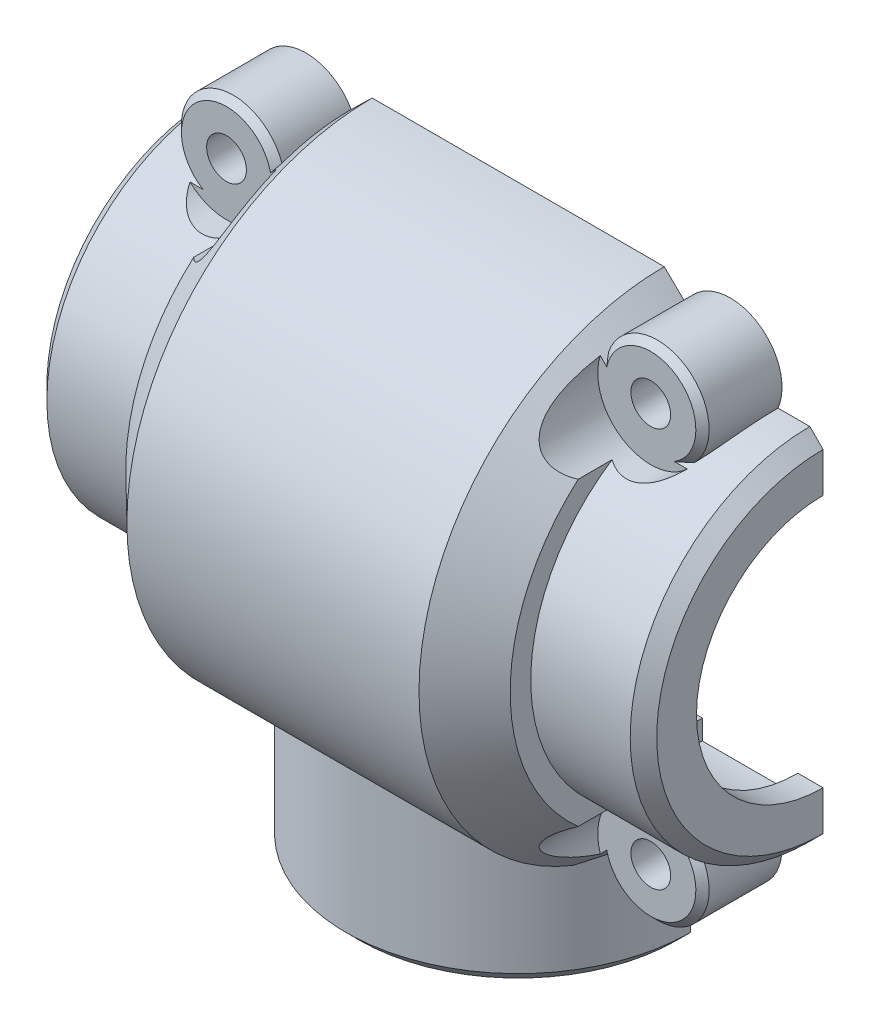
SolidWorks part; units mm, degrees
ref_plane "Front Plane" through (0, 0, 0) normal (0, 0, 1) x (1, 0, 0)
ref_plane "Top Plane" through (0, 0, 0) normal (0, 1, 0) x (1, 0, 0)
ref_plane "Right Plane" through (0, 0, 0) normal (1, 0, 0) x (0, 0, -1)
sketch "Sketch1" plane through (0, 0, 0) normal (0, 0, 1) x (1, 0, 0)
  line L0 (-12, 11.05) -> (-12, -11.05) construction
  line L1 (12, 11) -> (12, -11) construction
  line L2 (-12, 11.05) -> (-23, 11.05) construction
  line L3 (-23, 11.05) -> (-23, -11.05) construction
  line L4 (-23, -11.05) -> (-12, -11.05) construction
  line L5 (-21.1, 11.05) -> (-13.9, 11.05)
  line L6 (-12, 11.05) -> (-12, 14.05)
  line L7 (-12, 14.05) -> (-10, 16)
  line L8 (-10, 16) -> (0, 16)
  line L9 (-23, 13.55) -> (-14.5, 13.55)
  line L10 (-14.5, 13.55) -> (-14.5, 15.1041)
  line L11 (-14.5, 15.1041) -> (-11.017, 18.5)
  line L12 (-11.017, 18.5) -> (0, 18.5)
  line L13 (-23, 13.55) -> (-23, 11.05)
  line L14 (0, 18.5) -> (0, 0) construction
  line L15 (23, 13.55) -> (23, 11.05)
  line L16 (23, 13.55) -> (14.5, 13.55)
  line L17 (21.1, 11.05) -> (13.9, 11.05)
  line L18 (12, 11) -> (12, 14.05)
  line L19 (14.5, 13.55) -> (14.5, 15.1041)
  line L20 (14.5, 15.1041) -> (11.017, 18.5)
  line L21 (12, 14.05) -> (10, 16)
  line L22 (10, 16) -> (0, 16)
  line L23 (11.017, 18.5) -> (0, 18.5)
  line L24 (-23, 0) -> (12, 0) construction
  line L25 (-13.9, 11.05) -> (-12, 11.05) construction
  line L26 (-23, 11.05) -> (-21.1, 11.05) construction
  line L27 (-23, 11.05) -> (-23, 9.55)
  line L28 (-23, 9.55) -> (-21.1, 9.55)
  line L29 (-21.1, 11.05) -> (-21.1, 9.55)
  line L30 (-23, 11.05) -> (-21.1, 9.55) construction
  line L31 (-23, 9.55) -> (-21.1, 11.05) construction
  line L32 (-12, 11.05) -> (-13.9, 11.05) construction
  line L33 (-12, 11.05) -> (-12, 9.55)
  line L34 (-12, 9.55) -> (-13.9, 9.55)
  line L35 (-13.9, 11.05) -> (-13.9, 9.55)
  line L36 (-12, 11.05) -> (-13.9, 9.55) construction
  line L37 (-12, 9.55) -> (-13.9, 11.05) construction
  line L38 (-23, 11.05) -> (-21.1, 11.05) construction
  line L39 (-23, 11.05) -> (-12, 11.05) construction
  line L40 (23, 11.05) -> (23, 9.55)
  line L41 (23, 9.55) -> (21.1, 9.55)
  line L42 (21.1, 11.05) -> (21.1, 9.55)
  line L43 (12, 11) -> (12, 9.55)
  line L44 (12, 9.55) -> (13.9, 9.55)
  line L45 (13.9, 11.05) -> (13.9, 9.55)
  line L46 (13.9, 11.05) -> (12, 11) construction
  line L47 (23, 11.05) -> (21.1, 11.05) construction
  point P4 (-12, 0)
  point P5 (12, 0)
  point P30 (-22.05, 10.3)
  point P34 (-12.95, 10.3)
  point P35 (-12, 10.3)
  point P39 (12, 10.3)
  dimension "D1" = 22.1
  dimension "D2" = 22
  dimension "D3" = 12
  dimension "D4" = 12
  dimension "D5" = 11
  dimension "D6" = 3
  dimension "D7" = 10
  dimension "D8" = 16
  dimension "D10" = 1.5
  dimension "D11" = 1.9
  dimension "D12" = 1.9
  dimension "D13" = 1.5
  dimension "D9" = 2.5
revolve "Revolve1" add sketch "Sketch1" angle 180 about L24 region at (-21.5686, 10.3, 0)
sketch "Sketch2" plane through (0, 0, 0) normal (0, 1, 0) x (1, 0, 0)
  circle A0 centre (0, 0) radius 11
  circle A1 centre (0, 0) radius 4 construction
  dimension "D1" = 22
  dimension "D2" = 8
extrude "Cut-Extrude1" cut sketch "Sketch2" against normal through all
sketch "Sketch3" plane through (0, 0, 0) normal (0, 1, 0) x (1, 0, 0)
  line L0 (13, 0) -> (11, 0)
  line L1 (-11, 0) -> (-13, 0)
  line L2 (11, 0) -> (-11, 0) construction
  arc A0 (-11, 0) -> (11, 0) centre (0, 0) ccw
  arc A1 (-13, 0) -> (13, 0) centre (0, 0) ccw
  arc A2 (13, 0) -> (-13, 0) centre (0, 0) ccw construction
  arc A3 (11, 0) -> (-11, 0) centre (0, 0) ccw construction
  dimension "D1" = 11
  dimension "D2" = 13
extrude "Boss-Extrude1" add sketch "Sketch3" along normal up to surface (9 mm away) from offset 25 contours L0 A0 L1 A1 up to face at (-0.327, 2.2347, 10.6463) offset against normal yes
sketch "Sketch4" plane through (0, 0, 0) normal (0, 0, -1) x (-1, 0, 0)
  line L0 (23, -13.55) -> (14.5, -13.55) construction
  line L1 (14.5, -13.55) -> (14.5, -15.1041) construction
  line L2 (0, 0) -> (23, 0) construction
  line L3 (23, -9.55) -> (23, 9.55) construction
  line L4 (14.5, 13.55) -> (19.6, 13.55)
  line L5 (14.5, 15.1041) -> (14.5, 13.55)
  line L6 (13, 16.5666) -> (14.5, 15.1041)
  line L7 (13, 17.542) -> (13, 16.5666)
  line L8 (0, 18.5) -> (0, -25) construction
  line L9 (-11.017, 18.5) -> (11.017, 18.5) construction
  line L10 (-11, -25) -> (11, -25) construction
  line L11 (-14.5, -13.55) -> (-19.6, -13.55)
  line L12 (-14.5, -15.1041) -> (-14.5, -13.55)
  line L13 (-13, -16.5666) -> (-14.5, -15.1041)
  line L14 (-13, -17.542) -> (-13, -16.5666)
  line L15 (-13, 17.542) -> (-13, 16.5666)
  line L16 (13, -25) -> (13, -16.5666)
  line L17 (13, -16.5666) -> (14.5, -15.1041)
  line L18 (14.5, -15.1041) -> (14.5, -13.55)
  line L19 (14.5, -13.55) -> (23, -13.55)
  line L20 (23, -13.55) -> (23, -9.55)
  line L21 (23, -9.55) -> (21.1, -9.55)
  line L22 (21.1, -9.55) -> (21.1, -11.05)
  line L23 (21.1, -11.05) -> (13.9, -11.05)
  line L24 (13.9, -11.05) -> (13.9, -9.55)
  line L25 (13.9, -9.55) -> (12, -9.55)
  line L26 (12, -9.55) -> (12, -14.05)
  line L27 (12, -14.05) -> (11, -15.025)
  line L28 (11, -15.025) -> (11, -25)
  line L29 (11, -25) -> (13, -25)
  line L30 (13, -17.542) -> (13, -16.5666)
  line L31 (13, -16.5666) -> (14.5, -15.1041)
  line L32 (14.5, -15.1041) -> (14.5, -13.55)
  line L33 (14.5, -13.55) -> (19.6, -13.55)
  line L34 (-13, 16.5666) -> (-14.5, 15.1041)
  line L35 (-14.5, 15.1041) -> (-14.5, 13.55)
  line L36 (-14.5, 13.55) -> (-19.6, 13.55)
  arc A0 (13, -17.542) -> (19.6, -13.55) centre (16, -15.05) ccw
  circle A1 centre (16, -15.05) radius 1.5
  circle A2 centre (16, 15.05) radius 1.5
  arc A3 (13, 17.542) -> (19.6, 13.55) centre (16, 15.05) cw
  arc A4 (-13, 17.542) -> (-19.6, 13.55) centre (-16, 15.05) ccw
  circle A5 centre (-16, 15.05) radius 1.5
  circle A6 centre (-16, -15.05) radius 1.5
  arc A7 (-13, -17.542) -> (-19.6, -13.55) centre (-16, -15.05) cw
  circle A8 centre (16, -15.05) radius 3.9
  circle A9 centre (16, 15.05) radius 3.9
  circle A10 centre (-16, 15.05) radius 3.9
  circle A11 centre (-16, -15.05) radius 3.9
  line M24 (13, -25) -> (13, -16.5666)
  line M25 (13, -16.5666) -> (14.5, -15.1041)
  line M26 (14.5, -15.1041) -> (14.5, -13.55)
  line M27 (14.5, -13.55) -> (23, -13.55)
  dimension "D1" = 3
  dimension "D2" = 7.8
  dimension "D3" = 0
extrude "Boss-Extrude2" add sketch "Sketch4" against normal blind 6 contours L7 A9 L4 L5 L6 | A3 L7 L6 L5 A2 L4 | L4 A2 L5 | A1 A0 L33 M26 M25 M24 | L33 A8 L32 M24 M25 M26 M27 | A1 L32 M27 | A5 L35 L34 L15 A4 L36 | L36 A10 L15 L34 L35 | A5 L36 L35 | L11 A6 L12 | L14 A11 L11 L12 L13 | A7 L14 L13 L12 A6 L11 region at (-14.8351, 13.8851, 0) region at (-15.0756, 13.3566, 0) region at (-16.8249, 16.5395, 0) region at (14.8351, -13.8851, 0) region at (15.0756, -13.3566, 0) region at (16.8249, -16.5395, 0) region at (15.0756, 13.3566, 0) region at (16.8249, 16.5395, 0) region at (14.8351, 13.8851, 0) region at (-15.0756, -13.3566, 0) region at (-16.8249, -16.5395, 0) region at (-14.8351, -13.8851, 0)
sketch "Sketch5" plane through (0, 0, 6) normal (0, 0, 1) x (1, 0, 0)
  circle A0 centre (16, 15.05) radius 4
  circle A1 centre (16, -15.05) radius 4
  circle A2 centre (-16, -15.05) radius 4
  circle A3 centre (-16, 15.05) radius 4
  dimension "D1" = 8
extrude "Cut-Extrude2" cut sketch "Sketch5" along normal blind 16
chamfer "Chamfer1" distance 1 angle 45 3 edges at (0, -25, 13) (-23, 0, 13.55) (23, 0, 13.55)
sketch "Sketch6" plane through (0, 0, 0) normal (0, 0, -1) x (-1, 0, 0)
  line L0 (-11, -15.025) -> (-11, -16)
  line L1 (-11, -15.025) -> (-11, -25) construction
  line L2 (-11, -16) -> (11, -16)
  line L3 (11, -25) -> (11, -15.025) construction
  line L4 (11, -16) -> (11, -15.025)
  line L6 (-11, -25) -> (11, -25)
  line L7 (-11, -25) -> (-11, -23.2)
  line L8 (-11, -23.2) -> (11, -23.2)
  line L9 (11, -25) -> (11, -23.2)
  line L10 (-11, -25) -> (11, -23.2) construction
  line L11 (-11, -23.2) -> (11, -25) construction
  spline S0 degree 2 poles (-10, -15.3297) (0, -8.8064) (10, -15.3297) knots 0.014987 0.014987 0.014987 0.924078 0.924078 0.924078 weights 0.00533 0.01533 0.02533 construction
  spline S1 degree 2 poles (-10, -15.3297) (0, -8.8064) (10, -15.3297) knots 0.014987 0.014987 0.014987 0.924078 0.924078 0.924078 weights 0.00533 0.01533 0.02533
  spline S2 degree 3 poles (-184.3378, 969.3559) (183.9072, -1036.0234) (-155.9004, 1007.9439) (34.3542, -1013.9788) knots -0.054899 -0.054899 -0.054899 -0.054899 0.051001 0.051001 0.051001 0.051001 only from (-10, -15.3297) to (-11, -15.025) construction
  spline S3 degree 3 poles (-10, -15.3297) (-10.3273, -15.2102) (-10.661, -15.106) (-11, -15.025) knots 0 0 0 0 0.001046 0.001046 0.001046 0.001046
  spline S4 degree 3 poles (184.3378, 969.3559) (-183.9072, -1036.0234) (155.9004, 1007.9439) (-34.3542, -1013.9788) knots -0.054899 -0.054899 -0.054899 -0.054899 0.051001 0.051001 0.051001 0.051001 only from (10, -15.3297) to (11, -15.025) construction
  spline S5 degree 3 poles (10, -15.3297) (10.3273, -15.2102) (10.661, -15.106) (11, -15.025) knots 0 0 0 0 0.001046 0.001046 0.001046 0.001046
  point P15 (0, -24.1)
  dimension "D1" = 9
  dimension "D2" = 1.8
extrude "Boss-Extrude3" add sketch "Sketch6" against normal up to surface (4.5826 mm away) up to face at (-0.218, -17.8027, 4.1419)
sketch "Sketch7" plane through (0, -16, 0) normal (0, -1, 0) x (1, 0, 0)
  circle A0 centre (0, 0) radius 10
  dimension "D1" = 20
extrude "Cut-Extrude3" cut sketch "Sketch7" against normal blind 10 and the other way blind 10
chamfer "Chamfer2" distance 0.5 angle 45 4 edges at (-18.1012, -18.3355, 6) (18.1012, -18.3355, 6) (18.1012, 18.3355, 6) (-18.1012, 18.3355, 6)
